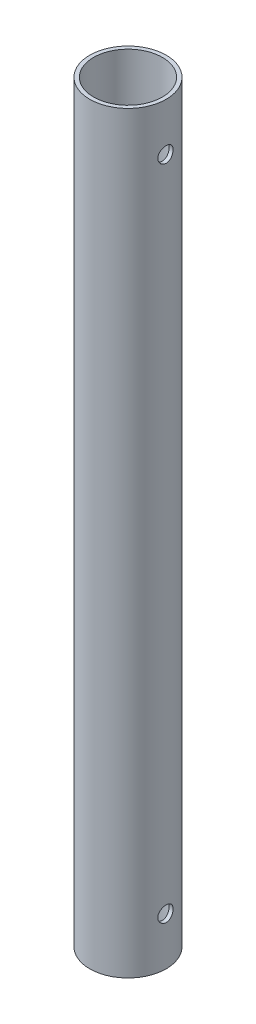
SolidWorks part; units mm, degrees
ref_plane "Front" through (0, 0, 0) normal (0, 0, 1) x (1, 0, 0)
ref_plane "Top" through (0, 0, 0) normal (0, 1, 0) x (1, 0, 0)
ref_plane "Right" through (0, 0, 0) normal (1, 0, 0) x (0, 0, -1)
sketch "Sketch1" plane through (0, 0, 0) normal (0, 1, 0) x (1, 0, 0)
  circle A0 centre (0, 0) radius 10
  circle A1 centre (0, 0) radius 9
  dimension "D1" = 20
  dimension "D2" = 1
extrude "Boss-Extrude1" add sketch "Sketch1" along normal blind 197
ref_plane "Plane1" through (10, 0, 0) normal (1, 0, 0) x (0, 0, -1)
sketch "Sketch2" plane through (10, 0, 0) normal (1, 0, 0) x (0, 0, -1)
  line L0 (0, 197) -> (0, 0) construction
  line L6 (9, 197) -> (-9, 197) construction
  circle A0 centre (0, 184.5) radius 2
  circle A1 centre (0, 12.5) radius 2
  point P9 (0, 0)
  dimension "D1" = 4
  dimension "D3" = 4
  dimension "D2" = 12.5
  dimension "D4" = 12.5
extrude "Cut-Extrude1" cut sketch "Sketch2" against normal through all contours L0 A0 | L0 A1 | A1 L0 | A0 L0
